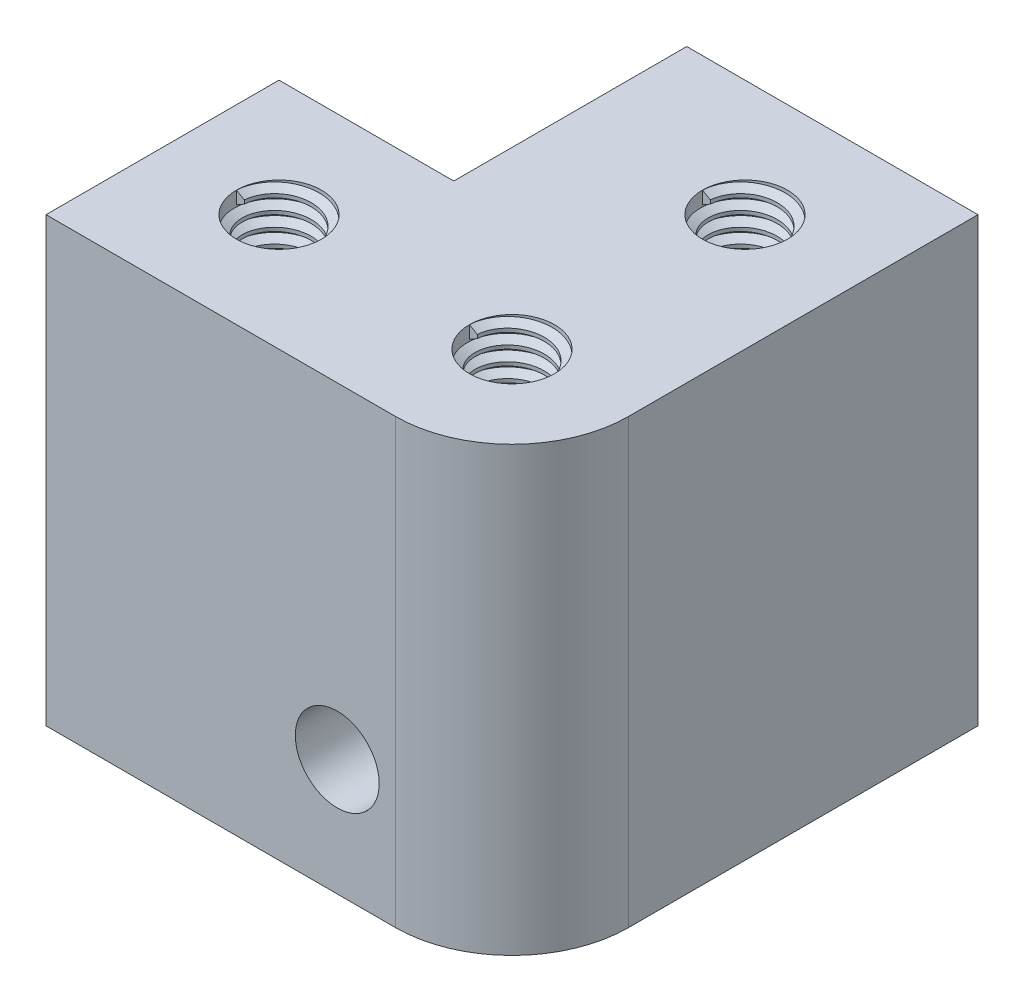
SolidWorks part; units mm, degrees
material "Copper"
ref_plane "Front Plane" through (0, 0, 0) normal (0, 0, 1) x (1, 0, 0)
ref_plane "Top Plane" through (0, 0, 0) normal (0, 1, 0) x (1, 0, 0)
ref_plane "Right Plane" through (0, 0, 0) normal (1, 0, 0) x (0, 0, -1)
sketch "Sketch1" plane through (0, 0, 0) normal (0, 1, 0) x (1, 0, 0)
  line L0 (0, 12.7) -> (9.525, 12.7)
  line L1 (0, 0) -> (19.05, 0)
  line L2 (0, 0) -> (0, 12.7)
  line L3 (9.525, 25.4) -> (25.4, 25.4)
  line L4 (25.4, 6.35) -> (25.4, 25.4)
  line L5 (9.525, 12.7) -> (9.525, 25.4)
  arc A0 (19.05, 0) -> (25.4, 6.35) centre (19.05, 6.35) ccw
  point P7 (25.4, 0)
  dimension "D3" = 6.35
  dimension "D1" = 25.4
  dimension "D2" = 25.4
  dimension "D4" = 15.875
  dimension "D5" = 12.7
extrude "Base Extrude" add sketch "Sketch1" along normal blind 24.13
sketch "Sketch3" plane through (0, 0, 0) normal (0, 0, 1) x (1, 0, 0)
  line L0 (0, 0) -> (19.05, 0) construction
  line L1 (25.4, 24.13) -> (25.4, 0) construction
  circle A0 centre (15.875, 6.35) radius 2.286
  dimension "D1" = 6.35
  dimension "D2" = 4.572
  dimension "D3" = 9.525
extrude "Axel Cut" cut sketch "Sketch3" against normal through all
sketch "Sketch4" plane through (0, 24.13, 0) normal (0, 1, 0) x (1, 0, 0)
  line L0 (25.4, 6.35) -> (25.4, 25.4) construction
  line L1 (0, 0) -> (19.05, 0) construction
  circle A0 centre (6.35, 6.35) radius 2.3177
  circle A1 centre (19.05, 6.35) radius 2.3178
  circle A2 centre (19.05, 19.05) radius 2.3178
  dimension "D1" = 4.6355
  dimension "D2" = 6.35
  dimension "D3" = 12.7
  dimension "D4" = 12.7
  dimension "D5" = 6.35
extrude "Cut-Extrude2" cut sketch "Sketch4" against normal blind 12.7
thread "Side Thread" pitch 0.7937 method extrude profile "Thread Profile1" start angle 0, offset 0, length 12.7, pitch 0.7937, diameter 4.6355
ref_plane "Plane1" through (4.0322, 24.13, -6.35) normal (0, 0, 1) x (-1, 0, 0)
sketch "Thread Profile1" plane through (4.0322, 24.13, -6.35) normal (0, 0, 1) x (-1, 0, 0)
  line L0 (0, 0) -> (0, 0.7937) construction
  line L11 (0, 0) -> (0, 0.6945)
  line L12 (0, 0.6945) -> (-0.4296, 0.4465)
  line L13 (-0.4296, 0.4465) -> (-0.4296, 0.248)
  line L15 (-0.4296, 0.248) -> (0, 0)
  line L17 (-0.4296, 0.3473) -> (0, 0.3473) construction
  point P2 (0, 0)
  dimension "Pitch" = 0.7937
  dimension "Profile_Angle" = 60
  dimension "Profile_Land" = 0.1984
  dimension "Profile_Height" = 0.4296
thread "Middle Thread" pitch 0.7937 method extrude profile "Thread Profile2" start angle 0, offset 0, length 12.7, pitch 0.7937, diameter 4.6355
ref_plane "Plane2" through (16.7322, 24.13, -6.35) normal (0, 0, 1) x (-1, 0, 0)
sketch "Thread Profile2" plane through (16.7322, 24.13, -6.35) normal (0, 0, 1) x (-1, 0, 0)
  line L0 (0, 0) -> (0, 0.7937) construction
  line L11 (0, 0) -> (0, 0.6945)
  line L12 (0, 0.6945) -> (-0.4296, 0.4465)
  line L13 (-0.4296, 0.4465) -> (-0.4296, 0.248)
  line L15 (-0.4296, 0.248) -> (0, 0)
  line L17 (-0.4296, 0.3473) -> (0, 0.3473) construction
  point P2 (0, 0)
  dimension "Pitch" = 0.7937
  dimension "Profile_Angle" = 60
  dimension "Profile_Land" = 0.1984
  dimension "Profile_Height" = 0.4296
thread "Front Thread" pitch 0.7937 method extrude profile "Thread Profile3" start angle 0, offset 0, length 12.7, pitch 0.7937, diameter 4.6355
ref_plane "Plane3" through (16.7322, 24.13, -19.05) normal (0, 0, 1) x (-1, 0, 0)
sketch "Thread Profile3" plane through (16.7322, 24.13, -19.05) normal (0, 0, 1) x (-1, 0, 0)
  line L0 (0, 0) -> (0, 0.7937) construction
  line L11 (0, 0) -> (0, 0.6945)
  line L12 (0, 0.6945) -> (-0.4296, 0.4465)
  line L13 (-0.4296, 0.4465) -> (-0.4296, 0.248)
  line L15 (-0.4296, 0.248) -> (0, 0)
  line L17 (-0.4296, 0.3473) -> (0, 0.3473) construction
  point P2 (0, 0)
  dimension "Pitch" = 0.7937
  dimension "Profile_Angle" = 60
  dimension "Profile_Land" = 0.1984
  dimension "Profile_Height" = 0.4296
